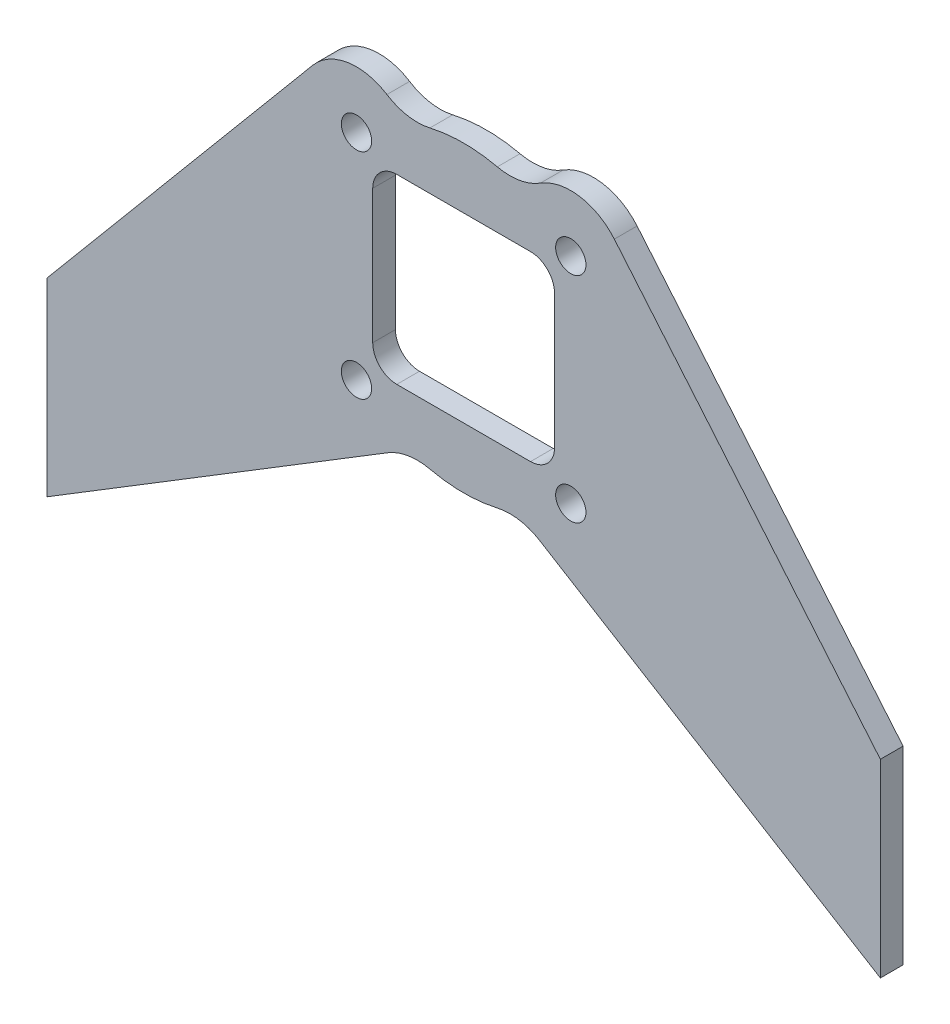
SolidWorks part; units mm, degrees
ref_plane "Front Plane" through (0, 0, 0) normal (0, 0, 1) x (1, 0, 0)
ref_plane "Top Plane" through (0, 0, 0) normal (0, 1, 0) x (1, 0, 0)
ref_plane "Right Plane" through (0, 0, 0) normal (1, 0, 0) x (0, 0, -1)
sketch "Sketch1" plane through (0, 0, 0) normal (0, 0, 1) x (1, 0, 0)
  line L0 (-19.8907, 18.9591) -> (-55, -22.9402)
  line L1 (19.8907, 18.9591) -> (55, -22.9402)
  line L2 (-55, -22.9402) -> (-55, -47.9402)
  line L3 (-55, -47.9402) -> (-10.2271, -20.5392)
  line L4 (8.825, 12) -> (-8.825, 12)
  line L5 (12, -8.825) -> (12, 8.825)
  line L6 (-8.825, -12) -> (8.825, -12)
  line L7 (-12, 8.825) -> (-12, -8.825)
  line L8 (8.825, 12) -> (-8.825, 12)
  line L9 (12, -8.825) -> (12, 8.825)
  line L10 (-8.825, -12) -> (8.825, -12)
  line L11 (-12, 8.825) -> (-12, -8.825)
  line L12 (10.2271, -20.5392) -> (55, -47.9402)
  line L13 (55, -47.9402) -> (55, -22.9402)
  circle A0 centre (-14.1421, 14.1421) radius 2 construction
  circle A1 centre (14.1421, 14.1421) radius 2 construction
  circle A2 centre (14.1421, -14.1421) radius 2 construction
  circle A3 centre (-14.1421, -14.1421) radius 2 construction
  circle A4 centre (-14.1421, 14.1421) radius 2
  circle A5 centre (14.1421, 14.1421) radius 2
  circle A6 centre (14.1421, -14.1421) radius 2
  circle A7 centre (-14.1421, -14.1421) radius 2
  arc A13 (-8.825, 12) -> (-12, 8.825) centre (-8.825, 8.825) ccw
  arc A14 (12, 8.825) -> (8.825, 12) centre (8.825, 8.825) ccw
  arc A15 (8.825, -12) -> (12, -8.825) centre (8.825, -8.825) ccw
  arc A16 (-4.4455, -19.4997) -> (4.4455, -19.4997) centre (0, 0) ccw
  arc A17 (10.1274, -20.4771) -> (4.4455, -19.4997) centre (6.1126, -26.812) ccw
  arc A18 (10.1274, -20.4771) -> (20.4771, -10.1274) centre (14.1421, -14.1421) ccw
  arc A19 (19.4997, -4.4455) -> (20.4771, -10.1274) centre (26.812, -6.1126) ccw
  arc A20 (19.4997, -4.4455) -> (19.4997, 4.4455) centre (0, 0) ccw
  arc A21 (20.4771, 10.1274) -> (19.4997, 4.4455) centre (26.812, 6.1126) ccw
  arc A22 (20.4771, 10.1274) -> (10.1274, 20.4771) centre (14.1421, 14.1421) ccw
  arc A23 (4.4455, 19.4997) -> (10.1274, 20.4771) centre (6.1126, 26.812) ccw
  arc A24 (4.4455, 19.4997) -> (-4.4455, 19.4997) centre (0, 0) ccw
  arc A25 (-10.1274, 20.4771) -> (-4.4455, 19.4997) centre (-6.1126, 26.812) ccw
  arc A26 (-10.1274, 20.4771) -> (-20.4771, 10.1274) centre (-14.1421, 14.1421) ccw
  arc A27 (-19.4997, 4.4455) -> (-20.4771, 10.1274) centre (-26.812, 6.1126) ccw
  arc A28 (-19.4997, 4.4455) -> (-19.4997, -4.4455) centre (0, 0) ccw
  arc A29 (-20.4771, -10.1274) -> (-19.4997, -4.4455) centre (-26.812, -6.1126) ccw
  arc A30 (-20.4771, -10.1274) -> (-10.1274, -20.4771) centre (-14.1421, -14.1421) ccw
  arc A31 (-4.4455, -19.4997) -> (-10.1274, -20.4771) centre (-6.1126, -26.812) ccw
  arc A32 (-4.4455, -19.4997) -> (4.4455, -19.4997) centre (0, 0) ccw
  arc A33 (10.1274, -20.4771) -> (4.4455, -19.4997) centre (6.1126, -26.812) ccw
  arc A34 (10.1274, -20.4771) -> (20.4771, -10.1274) centre (14.1421, -14.1421) ccw
  arc A35 (19.4997, -4.4455) -> (20.4771, -10.1274) centre (26.812, -6.1126) ccw
  arc A36 (19.4997, -4.4455) -> (19.4997, 4.4455) centre (0, 0) ccw
  arc A37 (20.4771, 10.1274) -> (19.4997, 4.4455) centre (26.812, 6.1126) ccw
  arc A38 (20.4771, 10.1274) -> (10.1274, 20.4771) centre (14.1421, 14.1421) ccw
  arc A39 (4.4455, 19.4997) -> (10.1274, 20.4771) centre (6.1126, 26.812) ccw
  arc A40 (4.4455, 19.4997) -> (-4.4455, 19.4997) centre (0, 0) ccw
  arc A41 (-10.1274, 20.4771) -> (-4.4455, 19.4997) centre (-6.1126, 26.812) ccw
  arc A42 (-10.1274, 20.4771) -> (-20.4771, 10.1274) centre (-14.1421, 14.1421) ccw
  arc A43 (-19.4997, 4.4455) -> (-20.4771, 10.1274) centre (-26.812, 6.1126) ccw
  arc A44 (-19.4997, 4.4455) -> (-19.4997, -4.4455) centre (0, 0) ccw
  arc A45 (-20.4771, -10.1274) -> (-19.4997, -4.4455) centre (-26.812, -6.1126) ccw
  arc A46 (-20.4771, -10.1274) -> (-10.1274, -20.4771) centre (-14.1421, -14.1421) ccw
  arc A47 (-4.4455, -19.4997) -> (-10.1274, -20.4771) centre (-6.1126, -26.812) ccw
  arc A48 (-12, -8.825) -> (-8.825, -12) centre (-8.825, -8.825) ccw
  arc A49 (-8.825, 12) -> (-12, 8.825) centre (-8.825, 8.825) ccw
  arc A50 (12, 8.825) -> (8.825, 12) centre (8.825, 8.825) ccw
  arc A51 (8.825, -12) -> (12, -8.825) centre (8.825, -8.825) ccw
  arc A52 (-12, -8.825) -> (-8.825, -12) centre (-8.825, -8.825) ccw
  dimension "D3" = 25
  dimension "D1" = 0
  dimension "D2" = 0
extrude "Boss-Extrude1" add sketch "Sketch1" along normal blind 3 contours A46 A45 A44 A43 A42 L0 L2 L3 | A47 A32 A33 A34 A35 A36 A37 A38 A39 A40 A41 A42 A43 A44 A45 A46 A52 L11 A49 L8 A50 L9 A51 L10 A7 A6 A5 A4 | A38 A37 A36 A35 A34 L12 L13 L1 region at (-35.6197, -18.4256, 0) region at (-15.2003, 20.9482, 0) region at (35.6197, -18.4256, 0)
